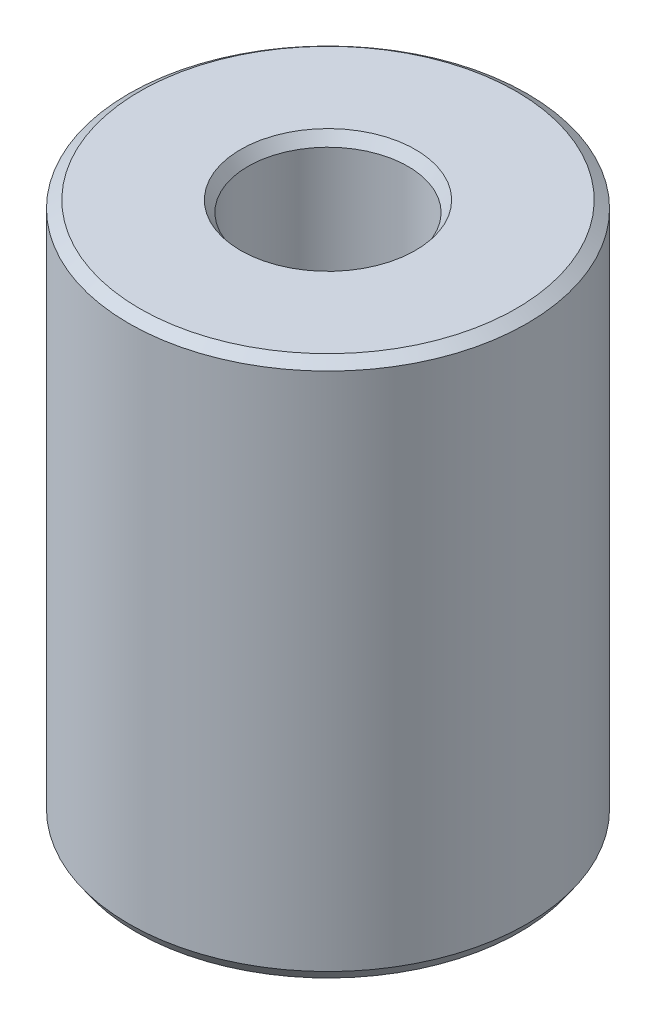
SolidWorks part; units mm, degrees
ref_plane "Front Plane" through (0, 0, 0) normal (0, 0, 1) x (1, 0, 0)
ref_plane "Top Plane" through (0, 0, 0) normal (0, 1, 0) x (1, 0, 0)
ref_plane "Right Plane" through (0, 0, 0) normal (1, 0, 0) x (0, 0, -1)
sketch "Sketch1" plane through (0, 0, 0) normal (0, 1, 0) x (1, 0, 0)
  circle A0 centre (0, 0) radius 25
  dimension "SLEEVE_OD" = 50
extrude "Boss-Extrude1" add sketch "Sketch1" along normal blind 67.5928
sketch "Sketch2" plane through (0, 0, 0) normal (0, 1, 0) x (1, 0, 0)
  circle A0 centre (0, 0) radius 10.0466
  dimension "BORE_D" = 20.0932
extrude "Cut-Extrude1" cut sketch "Sketch2" along normal through all
chamfer "Chamfer1" distance 0.9341 angle 55.595 4 edges at (0, 67.5928, 10.0466) (0, 0, 10.0466) (0, 0, 25) (0, 67.5928, 25) first distance on face at (0, 67.5928, 10.0466) first distance on face at (0, 0, 10.0466) first distance on face at (0, 67.5928, 25)
